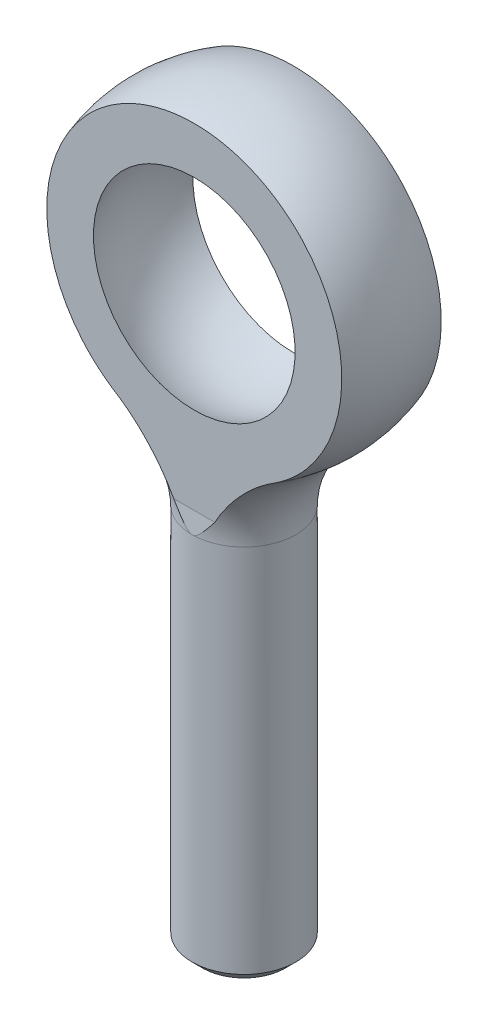
SolidWorks part; units mm, degrees
ref_plane "Front" through (0, 0, 0) normal (0, 0, 1) x (1, 0, 0)
ref_plane "Top" through (0, 0, 0) normal (0, 1, 0) x (1, 0, 0)
ref_plane "Right" through (0, 0, 0) normal (1, 0, 0) x (0, 0, -1)
sketch "Sketch1" plane through (0, 0, 0) normal (0, 0, 1) x (1, 0, 0)
  line L0 (0, 0) -> (0, -34.925)
  line L1 (0, -34.925) -> (4.7625, -34.925)
  line L2 (4.7625, -34.925) -> (4.7625, 0)
  line L3 (4.7625, 0) -> (0, 0)
  line L5 (0, 33.3375) -> (0, 0) construction
  line L6 (0, 33.3375) -> (14.2875, 33.3375) construction
  line L7 (14.2875, 33.3375) -> (14.2875, 19.05) construction
  line L8 (-4.7625, -34.925) -> (-4.7625, 0) construction
  line L9 (3.8092, -34.925) -> (4.7625, -33.9717)
  line L10 (4.8772, -34.8588) -> (4.8772, -35.918) construction
  line L11 (4.8772, -35.918) -> (3.9599, -35.3884) construction
  line L12 (3.9599, -35.3884) -> (4.8772, -34.8588) construction
  line L13 (3.9599, -35.3884) -> (4.0745, -35.3884) construction
  line L14 (4.8772, -35.3884) -> (4.7625, -35.3884) construction
  line L15 (4.0745, -35.4546) -> (4.0745, -35.3222) construction
  line L16 (4.7625, -35.8518) -> (4.7625, -34.925) construction
  line L17 (4.8198, -35.8849) -> (4.8198, -34.8919) construction
  arc A0 (8.5725, 7.62) -> (0, 33.3375) centre (0, 19.05) ccw construction
  circle A1 centre (0, 19.05) radius 4.7625 construction
  circle A2 centre (0, 19.05) radius 10.3187 construction
  circle A3 centre (0, 19.05) radius 10.8347 construction
  arc A4 (4.7625, 0) -> (8.5725, 7.62) centre (14.2875, 0) cw construction
  point P16 (-4.7625, -31.2179)
  point P28 (4.0745, -35.3884)
  point P31 (4.7625, -35.3884)
  point P34 (4.8198, -35.3884)
  dimension "Ball Dia" = 20.6375
  dimension "D1" = 21.6694
  dimension "ID" = 9.525
  dimension "D2" = 3.7071
  dimension "D3" = 45
  dimension "D4" = 0.9533
  dimension "Pitch" = 1.0592
  dimension "D5" = 0.1324
  dimension "Thread Size" = 9.525
  dimension "Overall Width" = 28.575
  dimension "Shank Thread Length" = 34.925
  dimension "Shank Center Length" = 53.975
sketch "Sketch2" plane through (0, 0, 0) normal (1, 0, 0) x (0, 0, -1)
  line L0 (-11.1125, 19.05) -> (11.1125, 19.05)
  line L2 (0, 25.7175) -> (0, 12.3825)
  line L3 (0, 23.8125) -> (0, 14.2875) construction
  line L4 (11.1125, 25.7175) -> (-11.1125, 25.7175)
  line L5 (11.1125, 23.8125) -> (-11.1125, 23.8125)
  line L6 (11.1125, 14.2875) -> (-11.1125, 14.2875)
  line L7 (11.1125, 12.3825) -> (-11.1125, 12.3825)
  line L8 (0, 19.05) -> (-11.1125, 24.8348) construction
  line L9 (0, 19.05) -> (-11.1125, 13.2652) construction
  point P0 (0, 23.8125)
  point P4 (0, 19.05)
  point P9 (0, 19.05)
  point P10 (0, 14.2875)
  point P18 (0, 23.8125)
  point P21 (0, 25.7175)
  point P24 (0, 14.2875)
  point P27 (0, 12.3825)
  dimension "Overall Thickness" = 22.225
  dimension "D1" = 13.335
  dimension "Maximum Ball Swivel" = 55
sketch "Sketch13" plane through (0, 0, 0) normal (0, 0, 1) x (1, 0, 0)
  line L0 (3.8092, -34.925) -> (4.7625, -33.9717) construction
  line L1 (3.8092, -34.925) -> (4.7625, -33.9717)
  line L4 (0, 0) -> (0, -34.925)
  line L5 (0, -34.925) -> (4.7625, -34.925)
  line L6 (4.7625, -34.925) -> (4.7625, 0)
  line L7 (4.7625, 0) -> (0, 0)
  line L8 (0, 0) -> (0, -34.925)
  line L9 (0, -34.925) -> (3.8092, -34.925)
  line L10 (4.7625, -33.9717) -> (4.7625, 0)
  line L11 (4.7625, 0) -> (0, 0)
  dimension "D1" = 0
revolve "Revolve4" add sketch "Sketch13" angle 360 about L8
sketch "Sketch4" plane through (0, 0, 0) normal (0, 0, 1) x (1, 0, 0)
  line L0 (4.7625, 0) -> (0, 0) construction
  line L1 (0, 8.7312) -> (0, 0)
  line L2 (0, 33.3375) -> (0, 0) construction
  line L3 (4.7625, 0) -> (0, 0)
  line L5 (0, 33.3375) -> (0, 29.3687)
  line L6 (0, 33.3375) -> (0, 35.8775) construction
  arc A0 (8.5725, 7.62) -> (0, 33.3375) centre (0, 19.05) ccw construction
  arc A1 (8.5725, 7.62) -> (0, 33.3375) centre (0, 19.05) ccw
  arc A2 (8.5725, 7.62) -> (4.7625, 0) centre (14.2875, 0) ccw construction
  arc A3 (8.5725, 7.62) -> (4.7625, 0) centre (14.2875, 0) ccw
  circle A4 centre (0, 19.05) radius 10.3187 construction
  arc A5 (0, 8.7312) -> (0, 29.3687) centre (0, 19.05) ccw
  dimension "D1" = 2.54
revolve "Revolve2" add sketch "Sketch4" angle 360 about L6
sketch "Sketch5" plane through (0, 0, 0) normal (1, 0, 0) x (0, 0, -1)
  line L0 (4.5641, 33.3375) -> (14.2875, 33.3375)
  line L1 (-4.5641, 33.3375) -> (4.5641, 33.3375) construction
  line L2 (-4.5641, 33.3375) -> (-4.5641, 1.8256)
  line L3 (-4.7625, 0) -> (4.7625, 0) construction
  line L4 (4.5641, 33.3375) -> (4.5641, 1.8256)
  line L5 (14.2875, 33.3375) -> (14.2875, 0)
  line L6 (14.2875, 0) -> (4.7625, 0)
  line L7 (-4.7625, 0) -> (-14.2875, 0)
  line L8 (-14.2875, 0) -> (-14.2875, 33.3375)
  line L9 (-14.2875, 33.3375) -> (-4.5641, 33.3375)
  line L10 (4.7625, 0) -> (4.5641, 1.8256)
  line L11 (-4.7625, 0) -> (-4.5641, 1.8256)
  line L12 (-4.5641, 1.8256) -> (4.5641, 1.8256) construction
  line L13 (0, 0) -> (0, 1.8256) construction
  arc A0 (8.5725, 7.62) -> (-8.5725, 7.62) centre (0, 19.05) ccw construction
  dimension "F" = 9.1281
  dimension "D2" = 1.8256
  dimension "D1" = 9.525
extrude "Cut-Extrude1" cut sketch "Sketch5" against normal through all and the other way through all
sketch "Sketch7" plane through (0, 0, 0) normal (0, 0, 1) x (1, 0, 0)
  line L0 (0, 29.3687) -> (0, 8.7312)
  line L1 (0, 33.3375) -> (0, 0) construction
  line L2 (0, 0) -> (0, 8.7312) construction
  arc A0 (0, 8.7312) -> (0, 29.3687) centre (0, 19.05) ccw
  circle A1 centre (0, 19.05) radius 10.3187 construction
sketch "Sketch10" plane through (0, 0, 0) normal (0, 0, 1) x (1, 0, 0)
  circle A0 centre (0, 19.05) radius 4.7625 construction
  circle A1 centre (0, 19.05) radius 4.7625
sketch "Sketch14" plane through (0, -34.925, 0) normal (0, -1, 0) x (1, 0, 0)
  circle A0 centre (0, 0) radius 4.7625
curve "Helix/Spiral1" pitch 1.0592 height 35.9842 turns 33.9736
sketch "Sketch15" plane through (0, 0, 0) normal (0, 0, 1) x (1, 0, 0)
  line L0 (4.0745, -35.3222) -> (4.8198, -34.8919)
  line L1 (4.8198, -34.8919) -> (4.8198, -35.8849)
  line L2 (4.8198, -35.8849) -> (4.0745, -35.4546)
  line L3 (4.0745, -35.4546) -> (4.0745, -35.3222)
sketch "Sketch16" plane through (0, 0, 0) normal (0, 1, 0) x (1, 0, 0)
  circle A0 centre (0, 0) radius 4.7625
move or copy body "Body-Move/Copy2" [suppressed] bodies to move or copy 112 122
move or copy body "Body-Move/Copy1" [suppressed] bodies to move or copy 112 122
equation "\"D1@Sketch1\"=\"Ball Dia@Sketch1\"*1.05"
equation "\"D1\"= \"ID@Sketch1\" / 20"
equation "\"D1@Sketch5\"= \"Thread Size@Sketch1\""
equation "\"D2@Sketch5\"=\"F@Sketch5\"/5"
equation "\"D5@Sketch1\"=\"Pitch@Sketch1\"/8"
equation "\"D4@Sketch1\"=\"Pitch@Sketch1\"*.9"
equation "\"D3@Helix/Spiral1\"= \"Shank Thread Length@Sketch1\" + \"Pitch@Sketch1\""
equation "\"D4@Helix/Spiral1\"=\"Pitch@Sketch1\""
equation "\"D2@Sketch1\"=\"Pitch@Sketch1\"*3.5"
equation "\"D1@Sketch2\"=\"ID@Sketch1\"*1.4"
